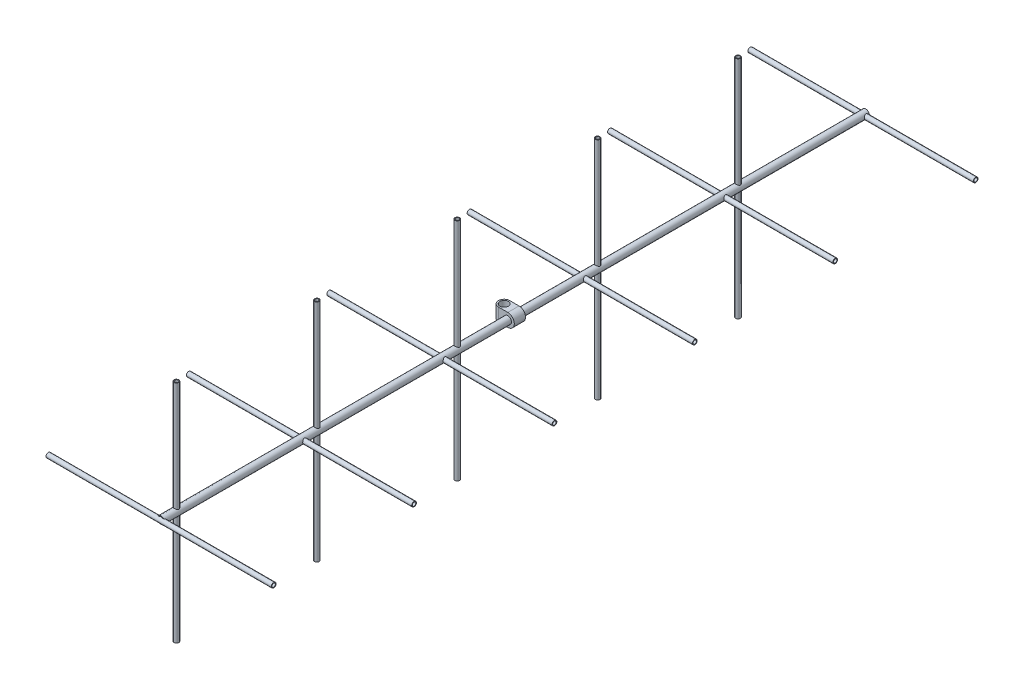
SolidWorks part; units mm, degrees
material "6061-T6 (SS)"
ref_plane "Front Plane" through (0, 0, 0) normal (0, 0, 1) x (1, 0, 0)
ref_plane "Top Plane" through (0, 0, 0) normal (0, 1, 0) x (1, 0, 0)
ref_plane "Right Plane" through (0, 0, 0) normal (1, 0, 0) x (0, 0, -1)
sketch "Sketch1" plane through (0, 0, 0) normal (0, 1, 0) x (1, 0, 0)
  line L0 (0, -1593.85) -> (0, 1593.85)
  line L1 (-509.5875, 1581.15) -> (509.5875, 1581.15)
  line L2 (-509.5875, 946.15) -> (509.5875, 946.15)
  line L3 (-509.5875, 311.15) -> (509.5875, 311.15)
  line L4 (-509.5875, -323.85) -> (509.5875, -323.85)
  line L5 (-509.5875, -958.85) -> (509.5875, -958.85)
  line L6 (-509.5875, -1593.85) -> (509.5875, -1593.85)
  line L7 (-509.5875, 1581.15) -> (-509.5875, 946.15) construction
  point P4 (0, 0)
  point P8 (0, 1581.15)
  point P11 (0, 1193.8)
  dimension "D1" = 3187.7
  dimension "D2" = 12.7
  dimension "D3" = 1019.175
  dimension "D4" = 6
  dimension "D5" = 635
sketch "Sketch2" plane through (0, 0, 0) normal (1, 0, 0) x (0, 0, -1)
  line L0 (-1524, -509.5875) -> (-1524, 509.5875)
  line L1 (-889, -509.5875) -> (-889, 509.5875)
  line L2 (-254, -509.5875) -> (-254, 509.5875)
  line L3 (381, -509.5875) -> (381, 509.5875)
  line L4 (1016, -509.5875) -> (1016, 509.5875)
  point P3 (-1524, 0)
  point P14 (-865.0215, 778.8673)
  point P15 (-1524, 0)
  point P16 (0, 0)
  dimension "D1" = 1019.175
  dimension "D2" = 1524
  dimension "D4" = 635
  dimension "D3" = 5
other "Pipe 1.0 SCH 40(1)" corner treatment miter
ref_plane "Plane1" through (0, 0, 1593.85) normal (0, 0, -1) x (-1, 0, 0)
sketch "Sketch11" plane through (0, 0, 1593.85) normal (0, 0, -1) x (-1, 0, 0)
  circle A0 centre (0, 0) radius 13.3223
  circle A1 centre (0, 0) radius 16.7005
  circle A2 centre (0, 0) radius 12.7 construction
  point P5 (0, 16.7005)
  point P6 (0, -16.7005)
  point P7 (-16.7005, 0)
  point P8 (16.7005, 0)
  point P9 (0, 0)
  dimension "In_dia" = 26.6446
  dimension "Out_dia" = 33.401
  dimension "D1" = 25.4
other "Pipe 0.5 SCH 40(1)" corner treatment miter
ref_plane "Plane2" through (-509.5875, 0, 1593.85) normal (1, 0, 0) x (0, 0, -1)
sketch "Sketch12" plane through (-509.5875, 0, 1593.85) normal (1, 0, 0) x (0, 0, -1)
  circle A0 centre (0, 0) radius 7.8994
  circle A1 centre (0, 0) radius 10.668
  circle A2 centre (0, 0) radius 6.35 construction
  point P5 (0, 10.668)
  point P6 (0, -10.668)
  point P7 (-10.668, 0)
  point P8 (10.668, 0)
  point P9 (0, 0)
  dimension "In_dia" = 15.7988
  dimension "Out_dia" = 21.336
  dimension "D1" = 12.7
sketch "Sketch14" plane through (0, 0, 0) normal (0, 0, 1) x (1, 0, 0)
  line L3 (-67.5005, -29.4005) -> (-67.5005, 29.4005)
  line L4 (0, 29.4005) -> (-67.5005, 29.4005)
  line L5 (-67.5005, -29.4005) -> (0, -29.4005)
  circle A0 centre (0, 0) radius 16.7005 construction
  circle A1 centre (0, 0) radius 16.7005
  arc A2 (0, -29.4005) -> (0, 29.4005) centre (0, 0) ccw
  circle A4 centre (0, 0) radius 29.4005 construction
  point P8 (29.4005, 0)
  dimension "D1" = 12.7
  dimension "D2" = 50.8
extrude "Boss-Extrude1" add sketch "Sketch14" along normal mid plane 50.8 separate body
fillet "Fillet1" radius 25.4 2 edges at (-67.5005, 0, -25.4) (-67.5005, 0, 25.4)
sketch "Sketch15" plane through (0, 29.4005, 0) normal (0, 1, 0) x (1, 0, 0)
  circle A0 centre (-42.1005, 0) radius 19.05
  arc A1 (-67.5005, 0) -> (-42.1005, -25.4) centre (-42.1005, 0) ccw construction
  dimension "D1" = 38.1
extrude "Cut-Extrude1" cut sketch "Sketch15" against normal through all
